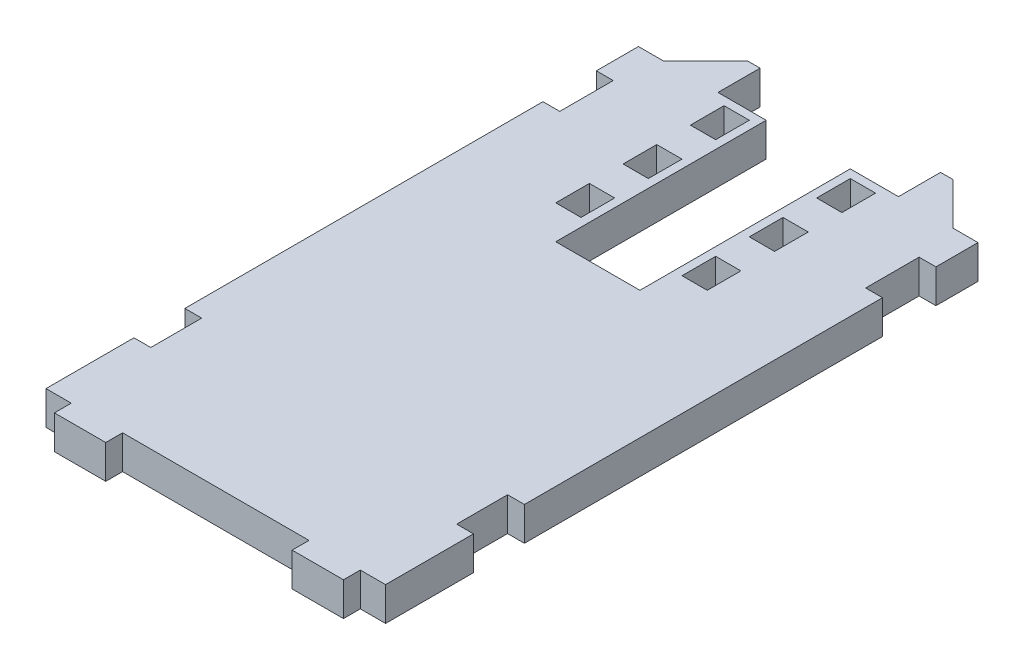
SolidWorks part; units mm, degrees
ref_plane "正面" through (0, 0, 0) normal (0, 0, 1) x (1, 0, 0)
ref_plane "平面" through (0, 0, 0) normal (0, 1, 0) x (1, 0, 0)
ref_plane "右側面" through (0, 0, 0) normal (1, 0, 0) x (0, 0, -1)
sketch "ｽｹｯﾁ1" plane through (0, 0, 0) normal (0, 1, 0) x (1, 0, 0)
  line L1 (0, 0) -> (40.35, 0)
  line L2 (0, 0) -> (0, 70.4)
  line L3 (0, 70.4) -> (40.35, 70.4)
  line L4 (40.35, 0) -> (40.35, 70.4)
  dimension "D1" = 40.35
  dimension "D2" = 70.4
extrude "ﾎﾞｽ - 押し出し1" add sketch "ｽｹｯﾁ1" along normal blind 4
sketch "ｽｹｯﾁ2" plane through (0, 4, 0) normal (0, 1, 0) x (1, 0, 0)
  line L0 (0, 70.4) -> (0, 0) construction
  line L1 (0, 16.5) -> (2, 16.5)
  line L2 (0, 16.5) -> (0, 10.45)
  line L3 (0, 10.45) -> (2, 10.45)
  line L4 (2, 16.5) -> (2, 10.45)
  line L5 (0, 0) -> (40.35, 0) construction
  line L6 (40.35, 0) -> (40.35, 70.4) construction
  line L7 (40.35, 16.5) -> (38.35, 16.5)
  line L8 (40.35, 16.5) -> (40.35, 10.45)
  line L9 (40.35, 10.45) -> (38.35, 10.45)
  line L10 (38.35, 16.5) -> (38.35, 10.45)
  line L11 (40.35, 70.4) -> (0, 70.4) construction
  line L12 (0, 65.4) -> (2, 65.4)
  line L13 (0, 65.4) -> (0, 59.05)
  line L14 (0, 59.05) -> (2, 59.05)
  line L15 (2, 65.4) -> (2, 59.05)
  line L17 (40.35, 65.4) -> (38.35, 65.4)
  line L18 (40.35, 65.4) -> (40.35, 59.05)
  line L19 (40.35, 59.05) -> (38.35, 59.05)
  line L20 (38.35, 65.4) -> (38.35, 59.05)
  line L21 (15.175, 70.4) -> (25.175, 70.4)
  line L22 (15.175, 70.4) -> (15.175, 45.4)
  line L23 (15.175, 45.4) -> (25.175, 45.4)
  line L24 (25.175, 70.4) -> (25.175, 45.4)
  dimension "D1" = 2
  dimension "D2" = 6.05
  dimension "D3" = 10.45
  dimension "D4" = 2
  dimension "D5" = 6.05
  dimension "D6" = 6.35
  dimension "D7" = 5
  dimension "D8" = 2
  dimension "D9" = 2
  dimension "D10" = 6.35
  dimension "D11" = 10
  dimension "D12" = 25
  dimension "D13" = 15.175
extrude "ｶｯﾄ - 押し出し3" cut sketch "ｽｹｯﾁ2" against normal through all
sketch "ｽｹｯﾁ4" plane through (0, 4, 0) normal (0, 1, 0) x (1, 0, 0)
  line L0 (15.175, 70.4) -> (15.175, 45.4) construction
  line L1 (11.175, 69.4) -> (14.175, 69.4)
  line L2 (11.175, 69.4) -> (11.175, 65.4)
  line L3 (11.175, 65.4) -> (14.175, 65.4)
  line L4 (14.175, 69.4) -> (14.175, 65.4)
  line L5 (15.175, 70.4) -> (0, 70.4) construction
  line L6 (25.175, 45.4) -> (25.175, 70.4) construction
  line L7 (11.175, 61.4) -> (14.175, 61.4)
  line L8 (11.175, 61.4) -> (11.175, 57.4)
  line L9 (11.175, 57.4) -> (14.175, 57.4)
  line L10 (14.175, 61.4) -> (14.175, 57.4)
  line L11 (11.175, 53.4) -> (14.175, 53.4)
  line L12 (11.175, 53.4) -> (11.175, 49.4)
  line L13 (11.175, 49.4) -> (14.175, 49.4)
  line L14 (14.175, 53.4) -> (14.175, 49.4)
  line L15 (26.175, 69.4) -> (29.175, 69.4)
  line L16 (26.175, 69.4) -> (26.175, 65.4)
  line L17 (26.175, 65.4) -> (29.175, 65.4)
  line L18 (29.175, 69.4) -> (29.175, 65.4)
  line L19 (40.35, 70.4) -> (25.175, 70.4) construction
  line L21 (26.175, 61.4) -> (29.175, 61.4)
  line L22 (26.175, 61.4) -> (26.175, 57.4)
  line L23 (26.175, 57.4) -> (29.175, 57.4)
  line L24 (29.175, 61.4) -> (29.175, 57.4)
  line L25 (26.175, 53.4) -> (29.175, 53.4)
  line L26 (26.175, 53.4) -> (26.175, 49.4)
  line L27 (26.175, 49.4) -> (29.175, 49.4)
  line L28 (29.175, 53.4) -> (29.175, 49.4)
  dimension "D1" = 4
  dimension "D2" = 3
  dimension "D3" = 1
  dimension "D4" = 1
  dimension "D5" = 4
  dimension "D6" = 4
  dimension "D7" = 3
  dimension "D8" = 4
  dimension "D9" = 4
  dimension "D10" = 3
  dimension "D11" = 4
  dimension "D12" = 1
  dimension "D13" = 1
  dimension "D14" = 3
  dimension "D17" = 1
extrude "ｶｯﾄ - 押し出し4" cut sketch "ｽｹｯﾁ4" against normal through all
sketch "ｽｹｯﾁ5" plane through (0, 0, -70.4) normal (0, 0, -1) x (-1, 0, 0)
  line L0 (-40.35, 4) -> (-25.175, 4) construction
  line L1 (-37.35, 4) -> (-30.9, 4)
  line L2 (-37.35, 4) -> (-37.35, 0)
  line L3 (-37.35, 0) -> (-30.9, 0)
  line L4 (-30.9, 4) -> (-30.9, 0)
  line L5 (-40.35, 0) -> (-25.175, 0) construction
  line L6 (-40.35, 4) -> (-40.35, 0) construction
  line L7 (-15.175, 4) -> (0, 4) construction
  line L8 (-9.45, 4) -> (-3, 4)
  line L9 (-9.45, 4) -> (-9.45, 0)
  line L10 (-9.45, 0) -> (-3, 0)
  line L11 (-3, 4) -> (-3, 0)
  line L12 (-15.175, 0) -> (0, 0) construction
  line L13 (0, 4) -> (0, 0) construction
  dimension "D1" = 3
  dimension "D2" = 6.45
  dimension "D3" = 3
  dimension "D4" = 6.45
extrude "ﾎﾞｽ - 押し出し2" add sketch "ｽｹｯﾁ5" along normal blind 5
chamfer "面取り1" distance 5 angle 45 2 edges at (3, 2, -75.4) (37.35, 2, -75.4)
sketch "ｽｹｯﾁ6" plane through (0, 0, 0) normal (0, 0, 1) x (1, 0, 0)
  line L0 (0, 4) -> (40.35, 4) construction
  line L1 (3, 4) -> (9.1, 4)
  line L2 (3, 4) -> (3, 0)
  line L3 (3, 0) -> (9.1, 0)
  line L4 (9.1, 4) -> (9.1, 0)
  line L5 (0, 0) -> (40.35, 0) construction
  line L6 (0, 4) -> (0, 0) construction
  line L7 (40.35, 4) -> (40.35, 0) construction
  line L8 (31.25, 4) -> (37.35, 4)
  line L9 (31.25, 4) -> (31.25, 0)
  line L10 (31.25, 0) -> (37.35, 0)
  line L11 (37.35, 4) -> (37.35, 0)
  dimension "D1" = 3
  dimension "D2" = 6.1
  dimension "D3" = 6.1
  dimension "D4" = 3
extrude "ﾎﾞｽ - 押し出し3" add sketch "ｽｹｯﾁ6" along normal blind 2
